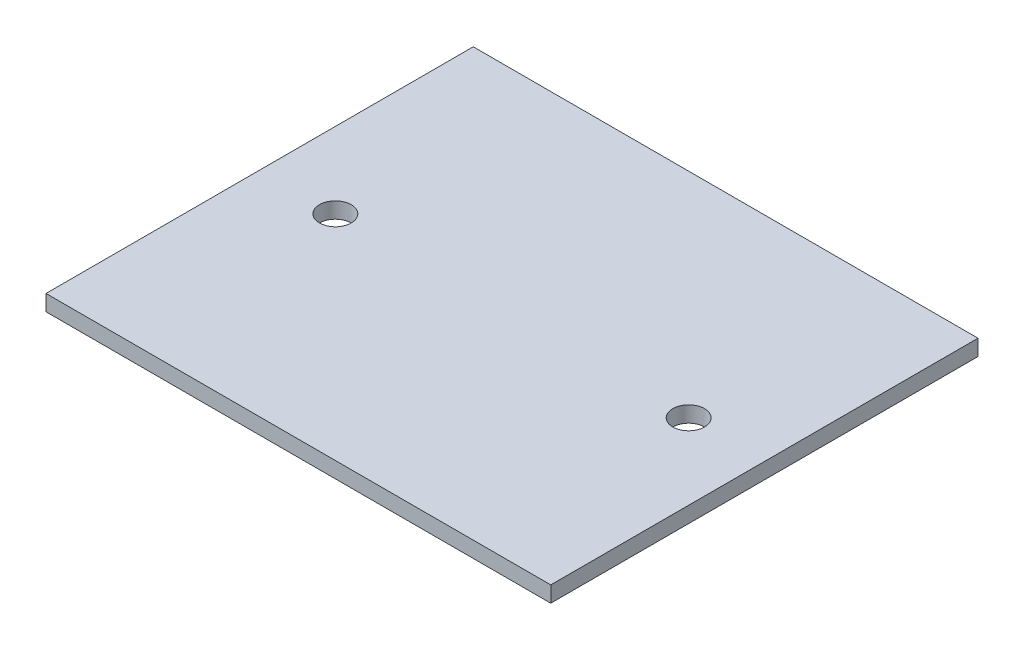
SolidWorks part; units mm, degrees
ref_plane "Front Plane" through (0, 0, 0) normal (0, 0, 1) x (1, 0, 0)
ref_plane "Top Plane" through (0, 0, 0) normal (0, 1, 0) x (1, 0, 0)
ref_plane "Right Plane" through (0, 0, 0) normal (1, 0, 0) x (0, 0, -1)
sketch "Sketch1" plane through (0, 0, 0) normal (0, 1, 0) x (1, 0, 0)
  line L1 (0, 0) -> (50.8, 0)
  line L2 (0, 0) -> (0, 43)
  line L3 (0, 43) -> (50.8, 43)
  line L4 (50.8, 0) -> (50.8, 43)
  circle A0 centre (7.62, 21.5) radius 1.6
  circle A1 centre (43.18, 21.5) radius 1.6
  point P9 (0, 21.5)
  dimension "D3" = 3.2
  dimension "D2" = 7.62
  dimension "D1" = 43
  dimension "50.8" = 50.8
  dimension "D4" = 35.56
extrude "Boss-Extrude1" add sketch "Sketch1" along normal blind 1.6002
